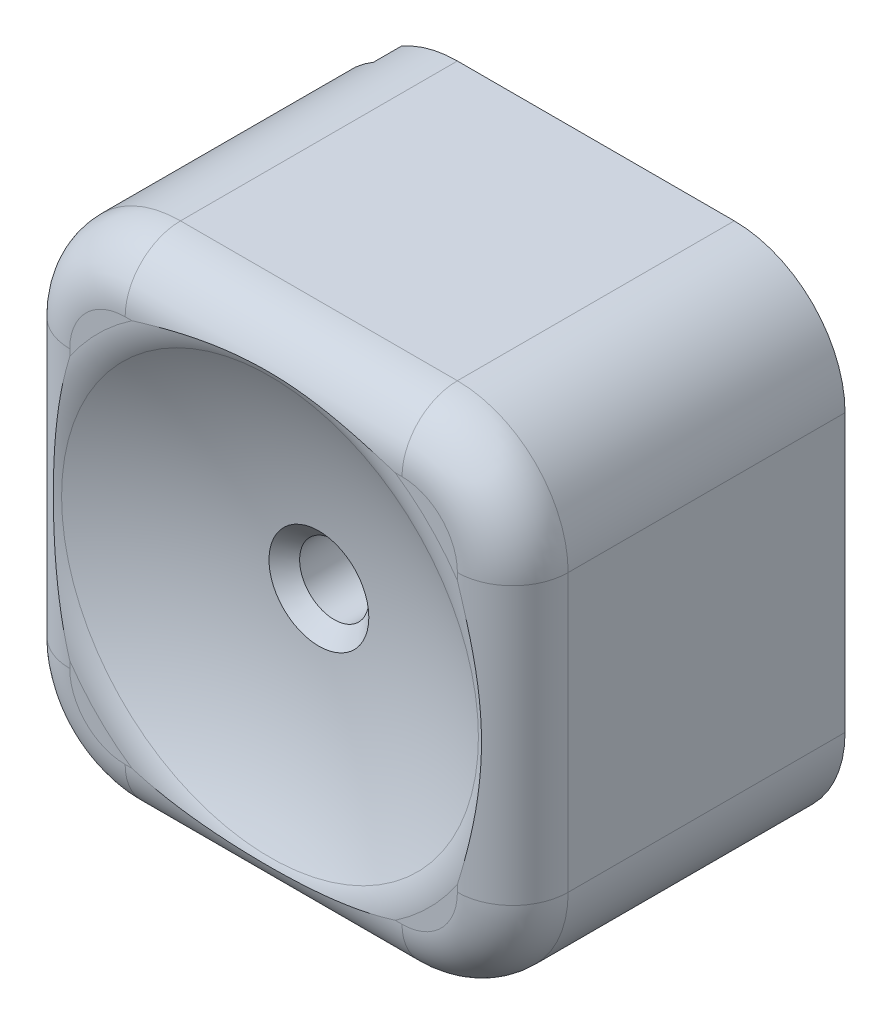
SolidWorks part; units mm, degrees
ref_plane "Front Plane" through (0, 0, 0) normal (0, 0, 1) x (1, 0, 0)
ref_plane "Top Plane" through (0, 0, 0) normal (0, 1, 0) x (1, 0, 0)
ref_plane "Right Plane" through (0, 0, 0) normal (1, 0, 0) x (0, 0, -1)
sketch "Sketch1" plane through (0, 0, 0) normal (0, 0, 1) x (1, 0, 0)
  line L1 (0, 0) -> (-18, 0)
  line L2 (0, 0) -> (0, 18)
  line L3 (0, 18) -> (-18, 18)
  line L4 (-18, 0) -> (-18, 18)
  dimension "D1" = 18
  dimension "D2" = 18
extrude "Boss-Extrude1" add sketch "Sketch1" along normal blind 13
fillet "Fillet1" radius 4 4 edges at (0, 0, 6.5) (-18, 0, 6.5) (-18, 18, 6.5) (0, 18, 6.5)
sketch "Sketch2" plane through (0, 0, 0) normal (0, 0, -1) x (-1, 0, 0)
  line L0 (9, 18) -> (9, 0) construction
  line L1 (4, 18) -> (14, 18) construction
  line L2 (14, 0) -> (4, 0) construction
  line L3 (0, 9) -> (18, 9) construction
  line L4 (0, 4) -> (0, 14) construction
  line L5 (18, 14) -> (18, 4) construction
  circle A0 centre (9, 9) radius 1.25
extrude "Cut-Extrude1" cut sketch "Sketch2" against normal blind 18
sketch "Sketch3" plane through (0, 0, 0) normal (0, 0, -1) x (-1, 0, 0)
  line L8 (1, 14) -> (1, 4)
  line L9 (4, 1) -> (14, 1)
  line L10 (17, 4) -> (17, 14)
  line L11 (14, 17) -> (4, 17)
  line L12 (1, 14) -> (1, 4)
  line L13 (4, 1) -> (14, 1)
  line L14 (17, 4) -> (17, 14)
  line L15 (14, 17) -> (4, 17)
  circle A0 centre (9, 9) radius 6
  arc A8 (1, 4) -> (4, 1) centre (4, 4) ccw
  arc A9 (14, 1) -> (17, 4) centre (14, 4) ccw
  arc A10 (17, 14) -> (14, 17) centre (14, 14) ccw
  arc A11 (4, 17) -> (1, 14) centre (4, 14) ccw
  arc A12 (1, 4) -> (4, 1) centre (4, 4) ccw
  arc A13 (14, 1) -> (17, 4) centre (14, 4) ccw
  arc A14 (17, 14) -> (14, 17) centre (14, 14) ccw
  arc A15 (4, 17) -> (1, 14) centre (4, 14) ccw
  dimension "D1" = 1
extrude "Cut-Extrude2" cut sketch "Sketch3" against normal blind 10
sketch "Sketch4" plane through (0, 0, 0) normal (0, 0, -1) x (-1, 0, 0)
  circle A5 centre (9, 9) radius 5.25
extrude "Cut-Extrude3" cut sketch "Sketch4" against normal blind 10
sketch "Sketch5" plane through (0, 0, 10) normal (0, 0, -1) x (-1, 0, 0)
  circle A0 centre (9, 9) radius 1.25
  circle A1 centre (9, 9) radius 1.75
extrude "Boss-Extrude2" add sketch "Sketch5" along normal blind 6
ref_plane "Plane1" through (0, 9, 0) normal (0, 1, 0) x (1, 0, 0)
sketch "Sketch7" plane through (0, 9, 0) normal (0, 1, 0) x (1, 0, 0)
  line L0 (-9, 0) -> (-9, -36.7523) construction
  line L1 (-4, 0) -> (-14, 0) construction
  line L2 (-9, -10.9) -> (-9, -43.1)
  arc A0 (-9, -43.1) -> (-9, -10.9) centre (-9, -27) ccw
revolve "Cut-Revolve4" cut sketch "Sketch7" angle 360 about L0
fillet "Fillet2" radius 2 9 edges at (-16.8284, 1.1716, 13) (-18, 9, 13) (-16.8284, 16.8284, 13) (-9, 18, 13) (-1.1716, 16.8284, 13) (0, 9, 13) (-1.1716, 1.1716, 13) (-9, 0, 13) (-1.0495, 9, 13)
sketch "Sketch9" plane through (0, 0, 0) normal (0, 0, -1) x (-1, 0, 0)
  line L1 (16.7071, 15.2929) -> (17.4457, 16.0315)
  line L2 (15.2929, 16.7071) -> (16.0315, 17.4457)
  arc A0 (18, 14) -> (14, 18) centre (14, 14) ccw construction
  arc A1 (17, 14) -> (14, 17) centre (14, 14) ccw construction
  arc A2 (17.4457, 16.0315) -> (16.0315, 17.4457) centre (14, 14) ccw
  arc A3 (16.7071, 15.2929) -> (15.2929, 16.7071) centre (14, 14) ccw
extrude "Cut-Extrude4" cut sketch "Sketch9" against normal blind 2
sketch "Sketch10" plane through (0, 0, 0) normal (0, 0, -1) x (-1, 0, 0)
  line L5 (-1.7803, 19.4257) -> (20.284, 19.4257)
  line L6 (-1.7803, 19.4257) -> (-1.7803, -2.1188)
  line L7 (-1.7803, -2.1188) -> (20.284, -2.1188)
  line L8 (20.284, 19.4257) -> (20.284, -2.1188)
extrude "Cut-Extrude5" cut sketch "Sketch10" against normal blind 1
chamfer "Chamfer1" distance 0.5 angle 45 10 edges at (-15, 9, 1) (-16.9259, 14.6628, 1) (-17, 9, 1) (-16.1213, 1.8787, 1) (-9, 1, 1) (-1.8787, 1.8787, 1) (-14.6628, 16.9259, 1) (-1, 9, 1) (-9, 17, 1) (-1.8787, 16.1213, 1)
chamfer "Chamfer2" distance 0.5 angle 45 1 edges at (-10.25, 9, 4)
chamfer "Chamfer3" distance 0.5 angle 45 1 edges at (-7.75, 9, 10.9486) first distance on face at (-10.25, 9, 4.5)
